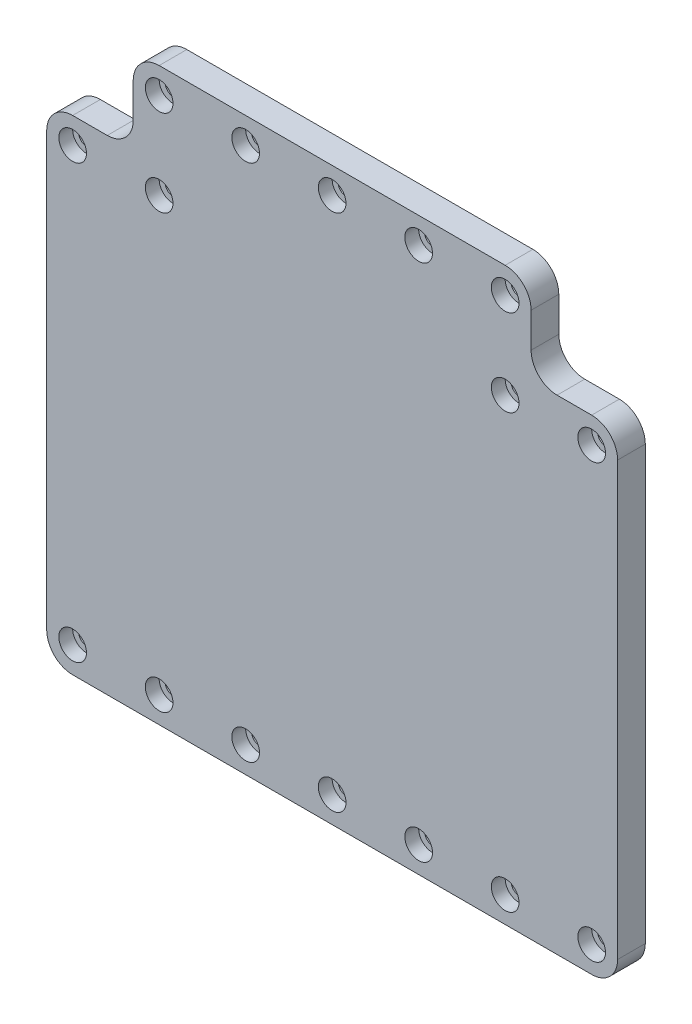
SolidWorks part; units mm, degrees
ref_plane "Front Plane" through (0, 0, 0) normal (0, 0, 1) x (1, 0, 0)
ref_plane "Top Plane" through (0, 0, 0) normal (0, 1, 0) x (1, 0, 0)
ref_plane "Right Plane" through (0, 0, 0) normal (1, 0, 0) x (0, 0, -1)
sketch "Sketch1" plane through (0, 0, 0) normal (0, 0, 1) x (1, 0, 0)
  line L0 (0, 101.5529) -> (0, -112.0648) construction
  line L1 (-50, 67.5) -> (50, 67.5)
  line L2 (57.5, 60) -> (57.5, 50)
  line L3 (65, 42.5) -> (75, 42.5)
  line L4 (82.5, 35) -> (82.5, -90)
  line L5 (75, -97.5) -> (-75, -97.5)
  line L6 (-82.5, -90) -> (-82.5, 35)
  line L7 (-75, 42.5) -> (-65, 42.5)
  line L8 (-57.5, 50) -> (-57.5, 60)
  arc A0 (-75, 42.5) -> (-82.5, 35) centre (-75, 35) ccw
  arc A1 (-57.5, 50) -> (-65, 42.5) centre (-65, 50) cw
  arc A2 (-50, 67.5) -> (-57.5, 60) centre (-50, 60) ccw
  arc A3 (57.5, 60) -> (50, 67.5) centre (50, 60) ccw
  arc A4 (65, 42.5) -> (57.5, 50) centre (65, 50) cw
  arc A5 (82.5, 35) -> (75, 42.5) centre (75, 35) ccw
  arc A6 (-75, -97.5) -> (-82.5, -90) centre (-75, -90) cw
  arc A7 (82.5, -90) -> (75, -97.5) centre (75, -90) cw
  point P15 (-57.5, 42.5)
  point P18 (-57.5, 67.5)
  dimension "D7" = 7.5
  dimension "D8" = 7.5
  dimension "D9" = 7.5
  dimension "D10" = 7.5
  dimension "D11" = 7.5
  dimension "D12" = 7.5
  dimension "D13" = 7.5
  dimension "D14" = 7.5
  dimension "D1" = 82.5
  dimension "D2" = 25
  dimension "D3" = 25
  dimension "D4" = 82.5
  dimension "D5" = 165
  dimension "D6" = 67.5
extrude "Boss-Extrude1" add sketch "Sketch1" against normal blind 8
sketch "Sketch2" plane through (0, 0, 0) normal (0, 0, 1) x (1, 0, 0)
  line L0 (-75, 35) -> (-50, 35) construction
  line L1 (-50, 35) -> (-50, 60) construction
  line L2 (-50, 60) -> (50, 60) construction
  line L3 (50, 60) -> (50, 35) construction
  line L4 (50, 35) -> (75, 35) construction
  line L5 (-65, 42.5) -> (-75, 42.5) construction
  line L6 (-57.5, 60) -> (-57.5, 50) construction
  line L7 (50, 67.5) -> (-50, 67.5) construction
  line L8 (57.5, 50) -> (57.5, 60) construction
  line L9 (75, 42.5) -> (65, 42.5) construction
  line L10 (-82.5, 35) -> (-82.5, -90) construction
  line L11 (82.5, -90) -> (82.5, 35) construction
  line L12 (-75, -90) -> (75, -90) construction
  line L13 (-75, -97.5) -> (75, -97.5) construction
  point P10 (-57.5, 55)
  point P17 (70, 42.5)
  point P22 (-25, 60)
  point P23 (-75, 35)
  point P24 (-50, 35)
  point P25 (-50, 60)
  point P26 (0, 60)
  point P27 (25, 60)
  point P29 (50, 60)
  point P30 (50, 35)
  point P31 (75, 35)
  point P35 (-25, -90)
  point P36 (-75, -90)
  point P37 (0, -90)
  point P38 (25, -90)
  point P39 (-50, -90)
  point P40 (50, -90)
  point P41 (75, -90)
  dimension "D1" = 7.5
  dimension "D2" = 7.5
  dimension "D3" = 7.5
  dimension "D4" = 7.5
  dimension "D5" = 7.5
  dimension "D6" = 7.5
  dimension "D7" = 7.5
  dimension "D8" = 25
  dimension "D9" = 25
  dimension "D10" = 25
  dimension "D11" = 7.5
  dimension "D12" = 7.5
  dimension "D13" = 7.5
  dimension "D14" = 25
  dimension "D15" = 25
  dimension "D16" = 25
  dimension "D17" = 25
  dimension "D18" = 25
  dimension "D19" = 25
hole_wizard "CBORE for M4 SHCS1" positions "Sketch2" profile "Sketch3" counterbore size "M4" standard "ANSI Metric" end condition through all
sketch "Sketch3" plane through (75, -90, 0) normal (1, 0, 0) x (0, -1, 0)
  line L0 (0, 0) -> (0, 8)
  line L1 (0, 8) -> (2.25, 8)
  line L3 (2.25, 8) -> (2.25, 4)
  line L4 (2.25, 4) -> (4, 4)
  line L5 (4, 4) -> (4, 0)
  line L7 (4, 0) -> (0, 0)
  line L11 (0, -6.35) -> (0, 107.95) construction
  dimension "Thru Hole Dia." = 4.5
  dimension "Thru Hole Depth" = 8
  dimension "C'Bore Dia." = 8
  dimension "C'Bore Depth" = 4
